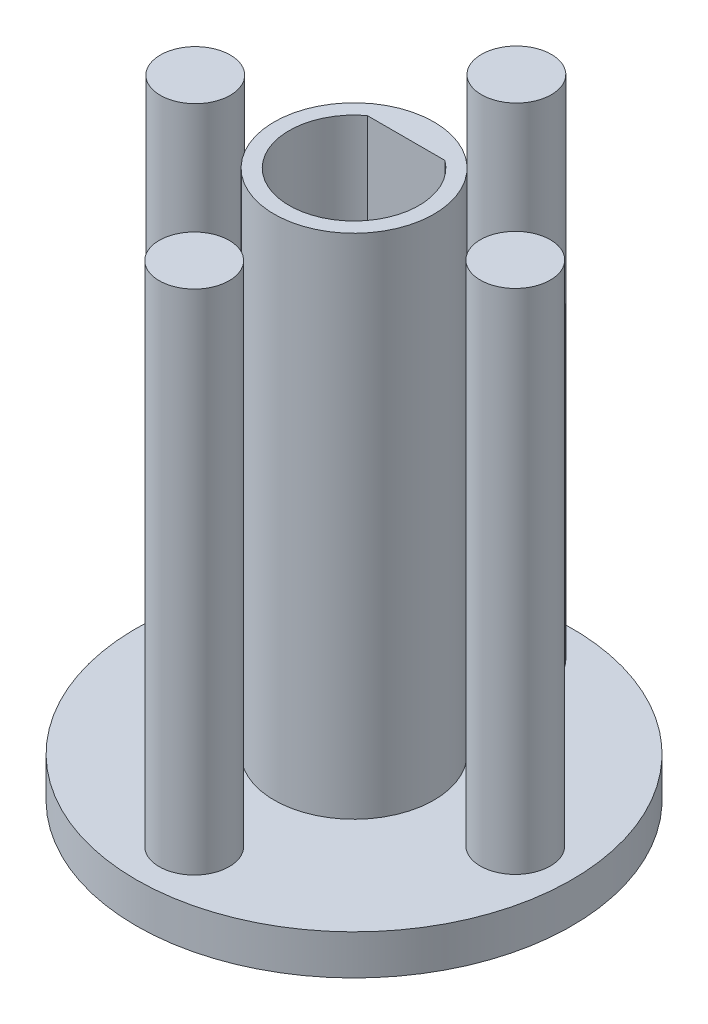
SolidWorks part; units mm, degrees
ref_plane "Front Plane" through (0, 0, 0) normal (0, 0, 1) x (1, 0, 0)
ref_plane "Top Plane" through (0, 0, 0) normal (0, 1, 0) x (1, 0, 0)
ref_plane "Right Plane" through (0, 0, 0) normal (1, 0, 0) x (0, 0, -1)
sketch "Sketch3" plane through (0, 0, 0) normal (0, 1, 0) x (1, 0, 0)
  line L0 (-7.9995, 0.0532) -> (0.009, 8.1156) construction
  line L1 (0.009, 8.1156) -> (8.0177, 0.0533) construction
  line L2 (8.0177, 0.0533) -> (0.0092, -8.0091) construction
  line L3 (0.0092, -8.0091) -> (-7.9995, 0.0532) construction
  line L7 (18.7783, 0.0532) -> (-25.5315, 0.0532) construction
  line L8 (9.7482, 0.0532) -> (10.8982, 0.0532)
  line L9 (-1.9426, 2.6055) -> (1.9426, 2.6055)
  line L11 (0.009, -13.1564) -> (0.009, 16.0208) construction
  circle A0 centre (0, 0) radius 10.9
  circle A1 centre (0.009, 8.1156) radius 1.75
  circle A2 centre (8.0177, 0.0533) radius 1.75
  circle A3 centre (0.0092, -8.0091) radius 1.75
  circle A4 centre (-7.9995, 0.0532) radius 1.75
  circle A5 centre (0, 0) radius 4
  arc A6 (-1.9426, 2.6055) -> (1.9426, 2.6055) centre (0, 0) ccw
  dimension "D1" = 21.8
extrude "Boss-Extrude1" add sketch "Sketch3" along normal blind 27.4 contours A4 | A3 | A2 | A1 | A6 L9 | A5
extrude "Boss-Extrude2" add sketch "Sketch3<17>" along normal blind 2 contours A0
sketch "Sketch3<17>" plane through (0, 0, 0) normal (0, 1, 0) x (1, 0, 0) same geometry as "Sketch3"
